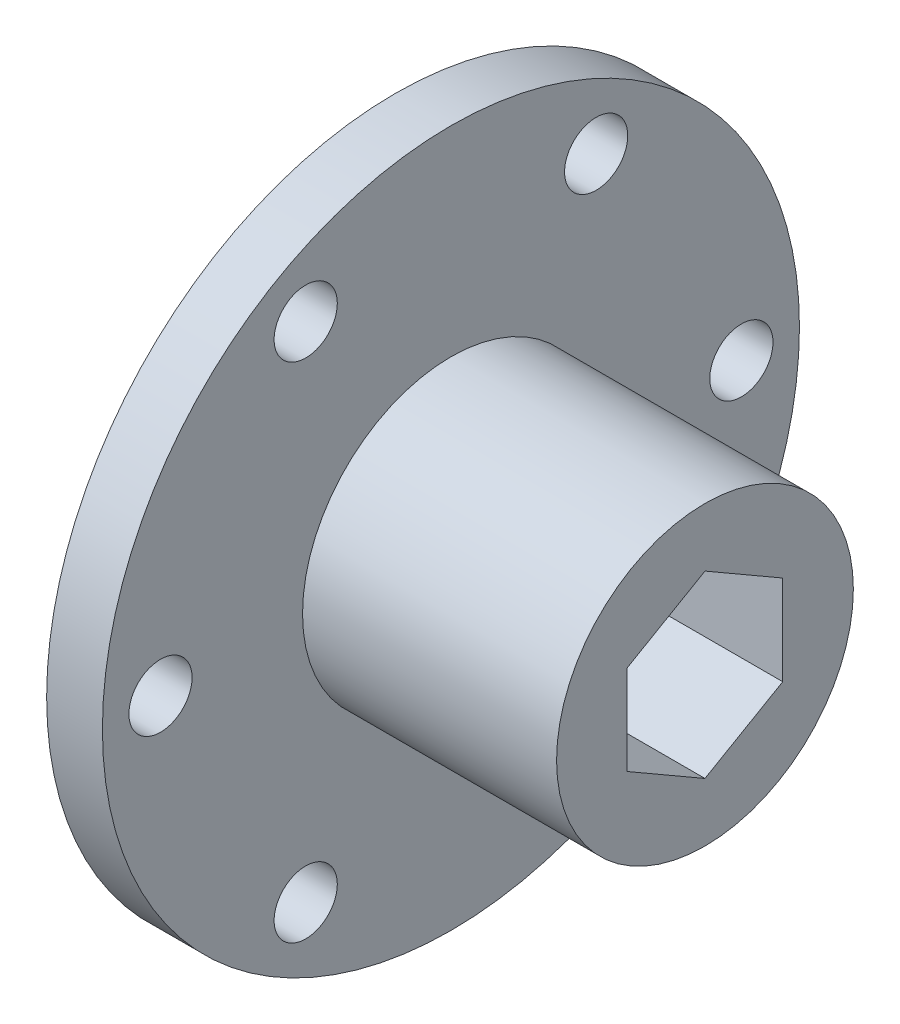
SolidWorks part; units mm, degrees
material "6061-T6 (SS)"
ref_plane "Front Plane" through (0, 0, 0) normal (0, 0, 1) x (1, 0, 0)
ref_plane "Top Plane" through (0, 0, 0) normal (0, 1, 0) x (1, 0, 0)
ref_plane "Right Plane" through (0, 0, 0) normal (1, 0, 0) x (0, 0, -1)
ref_plane "Plane1" through (0, 0, 0) normal (0, 0, -1) x (-1, 0, 0)
sketch "Sketch1" plane through (0, 0, 0) normal (0, 0, -1) x (-1, 0, 0)
  line L0 (13.0351, 28.575) -> (13.0351, 0)
  line L1 (13.0351, 0) -> (17.6071, 0)
  line L2 (17.6071, 0) -> (17.6071, 28.575)
  line L3 (17.6071, 28.575) -> (13.0351, 28.575)
  line L4 (13.0351, 0) -> (17.6071, 0) construction
revolve "Revolve1" add sketch "Sketch1" angle 360 about L4 reverse direction yes
sketch "Sketch2" plane through (-13.0351, 0, 0) normal (1, 0, 0) x (0, 0, -1)
  circle A0 centre (0, 0) radius 12.1666
extrude "Boss-Extrude1" add sketch "Sketch2" along normal blind 20.828
sketch "Sketch3" plane through (7.7929, 0, 0) normal (1, 0, 0) x (0, 0, -1)
  line L0 (0, -7.3617) -> (6.3754, -3.6809)
  line L1 (6.3754, -3.6809) -> (6.3754, 3.6808)
  line L2 (6.3754, 3.6808) -> (0, 7.3617)
  line L3 (0, 7.3617) -> (-6.3754, 3.6808)
  line L4 (-6.3754, 3.6808) -> (-6.3754, -3.6809)
  line L5 (-6.3754, -3.6809) -> (0, -7.3617)
extrude "Cut-Extrude1" cut sketch "Sketch3" against normal through all
hole_wizard "Hole1" positions "Sketch5" profile "Sketch4" legacy
sketch "Sketch5" plane through (-13.0351, 0, 0) normal (1, 0, 0) x (0, 0, -1)
  point P0 (-23.8125, 0)
sketch "Sketch4" plane through (-13.0351, 0, 23.8125) normal (0, 1, 0) x (0, 0, -1)
  line L0 (0, 0) -> (0, 4.572)
  line L1 (0, 4.572) -> (2.5908, 4.572)
  line L2 (2.5908, 4.572) -> (2.5908, 0)
  line L3 (2.5908, 0) -> (0, 0)
  line L4 (0, 110) -> (0, -10) construction
  dimension "Diameter" = 5.1816
  dimension "Depth" = 4.572
sketch3d "3DSketch1"
  point P0 (84.6789, 0, 0)
  point P1 (-15.3211, 0, 0)
ref_axis "Axis1" through (84.6789, 0, 0) along (-1, 0, 0)
pattern_circular "CirPattern1" count 6 over 360 about axis through (84.6789, 0, 0) along (-1, 0, 0) of "Hole1"
